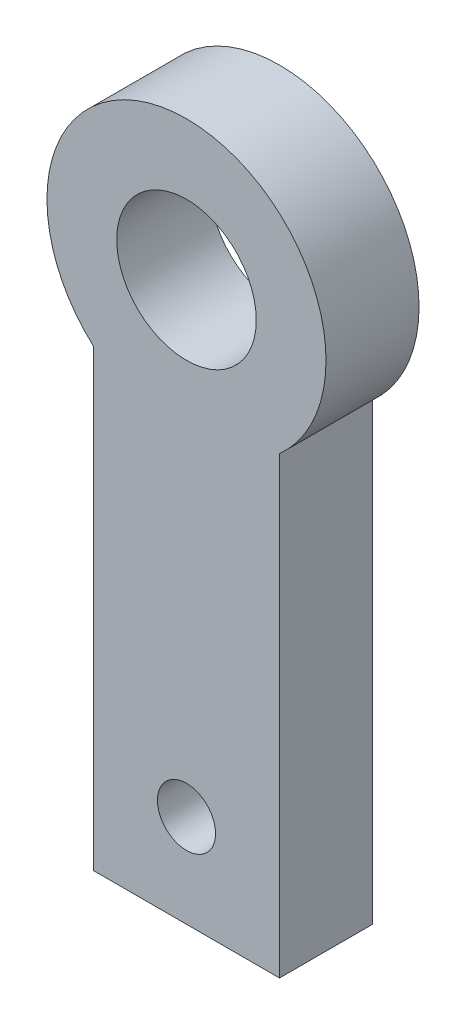
SolidWorks part; units mm, degrees
ref_plane "Front Plane" through (0, 0, 0) normal (0, 0, 1) x (1, 0, 0)
ref_plane "Top Plane" through (0, 0, 0) normal (0, 1, 0) x (1, 0, 0)
ref_plane "Right Plane" through (0, 0, 0) normal (1, 0, 0) x (0, 0, -1)
ref_plane "Horn Bottom" through (0, 0, 13.2) normal (0, 0, 1) x (1, 0, 0)
sketch "Horn Arm Sketch" plane through (0, 0, 13.2) normal (0, 0, 1) x (1, 0, 0)
  line L0 (-95, 59.4) -> (-87, 59.4)
  line L1 (-87, 59.4) -> (-87, 83.4)
  line L2 (-87, 83.4) -> (-95, 83.4)
  line L3 (-95, 83.4) -> (-95, 59.4)
extrude "Horn Arm" add sketch "Horn Arm Sketch" along normal blind 4
sketch "Horn Hub Sketch" plane through (0, 0, 13.2) normal (0, 0, 1) x (1, 0, 0)
  circle A0 centre (-91, 83.4) radius 6
extrude "Horn Hub" add sketch "Horn Hub Sketch" along normal blind 4
sketch "Shaft Bore Sketch" plane through (0, 0, 13.2) normal (0, 0, 1) x (1, 0, 0)
  circle A0 centre (-91, 83.4) radius 3
extrude "Shaft Bore" cut sketch "Shaft Bore Sketch" along normal blind 4
sketch "Ball Stud Hole Sketch" plane through (0, 0, 13.2) normal (0, 0, 1) x (1, 0, 0)
  circle A0 centre (-91, 63.4) radius 1.25
extrude "Ball Stud Hole" cut sketch "Ball Stud Hole Sketch" along normal blind 4
ref_plane "Shaft Plane X" through (-91, 0, 0) normal (1, 0, 0) x (0, 0, -1)
ref_plane "Shaft Plane Y" through (0, 83.4, 0) normal (0, 1, 0) x (1, 0, 0)
ref_axis "Shaft Axis" through (-91, 83.4, 17.4) along (0, 0, -1)
